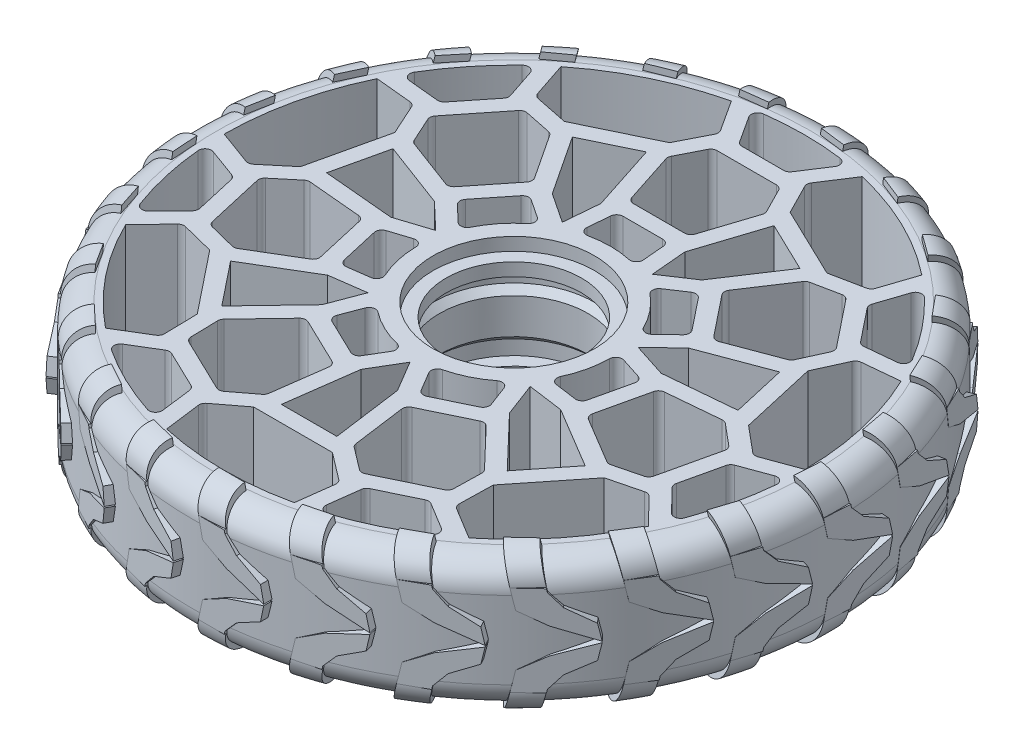
SolidWorks part; units mm, degrees
ref_plane "Front Plane" through (0, 0, 0) normal (0, 0, 1) x (1, 0, 0)
ref_plane "Top Plane" through (0, 0, 0) normal (0, 1, 0) x (1, 0, 0)
ref_plane "Right Plane" through (0, 0, 0) normal (1, 0, 0) x (0, 0, -1)
sketch "Sketch1" plane through (0, 0, 0) normal (0, 1, 0) x (1, 0, 0)
  circle A0 centre (0, 0) radius 19.05
  circle A1 centre (0, 0) radius 57.15
  circle A2 centre (0, 0) radius 63.5
  dimension "D1" = 127
  dimension "D2" = 114.3
  dimension "D3" = 38.1
extrude "Boss-Extrude1" add sketch "Sketch1" along normal blind 25.4 contours A2 A1 | A0
sketch "Sketch2" plane through (0, 25.4, 0) normal (0, 1, 0) x (1, 0, 0)
  line L1 (-5.0658, 25.4) -> (5.0658, 25.4)
  line L3 (-5.9462, 28.575) -> (5.9462, 28.575)
  line L4 (5.9462, 28.575) -> (9.6276, 39.9052)
  line L5 (9.6276, 39.9052) -> (6.6026, 45.8421)
  line L6 (6.6026, 45.8421) -> (-6.6026, 45.8421)
  line L7 (-6.6026, 45.8421) -> (-9.6276, 39.9052)
  line L8 (-9.6276, 39.9052) -> (-5.9462, 28.575)
  line L9 (-9.525, 56.3507) -> (-4.7625, 49.0171)
  line L10 (-4.7625, 49.0171) -> (4.7625, 49.0171)
  line L11 (4.7625, 49.0171) -> (9.525, 56.3507)
  line L12 (-8.253, 25.4) -> (-13.0536, 40.1748)
  line L13 (-13.0536, 40.1748) -> (-8.5483, 49.0171)
  line L14 (-8.5483, 49.0171) -> (-12.8757, 55.6807)
  line L15 (12.8757, 55.6807) -> (8.5483, 49.0171)
  line L16 (8.5483, 49.0171) -> (13.0536, 40.1748)
  line L17 (13.0536, 40.1748) -> (8.253, 25.4)
  line L18 (0, 0) -> (66.475, 0) construction
  line L19 (0, 0) -> (5.8868, 18.1176) construction
  line L20 (0, 0) -> (-5.8868, 18.1176) construction
  line L21 (0, 0) -> (-66.2004, 0) construction
  line L22 (-9.0065, 16.7864) -> (-8.253, 25.4)
  line L23 (-8.253, 25.4) -> (-20.404, 62.7971) construction
  line L24 (-5.0658, 25.4) -> (-5.6977, 18.178)
  line L25 (8.253, 25.4) -> (9.0065, 16.7864)
  line L26 (8.253, 25.4) -> (19.9506, 61.4016) construction
  line L27 (5.0658, 25.4) -> (5.6977, 18.178)
  circle A0 centre (0, 0) radius 19.05 construction
  circle A1 centre (0, 0) radius 57.15 construction
  arc A2 (-9.0065, 16.7864) -> (-5.6977, 18.178) centre (0, 0) cw
  arc A3 (5.6977, 18.178) -> (9.0065, 16.7864) centre (0, 0) cw
  arc A4 (-12.8757, 55.6807) -> (-9.525, 56.3507) centre (0, 0) cw
  arc A5 (9.525, 56.3507) -> (12.8757, 55.6807) centre (0, 0) cw
  point P35 (0, 49.0171)
  point P36 (0, 45.8421)
  point P42 (0, 28.575)
  dimension "D1" = 72
  dimension "D2" = 72
  dimension "D7" = 3.175
  dimension "D8" = 45
  dimension "D9" = 120
  dimension "D11" = 45
  dimension "D13" = 120
  dimension "D14" = 3.175
  dimension "D3" = 3.175
  dimension "D5" = 3.175
  dimension "D4" = 3.175
  dimension "D6" = 95
  dimension "D18" = 95
  dimension "D19" = 19.05
  dimension "D15" = 3.175
  dimension "D10" = 3.175
  dimension "D12" = 3.175
  dimension "D16" = 9.525
  dimension "D17" = 25.4
extrude "Boss-Extrude2" add sketch "Sketch2" against normal up to surface (25.4 mm away) up to face at (0, 0, 19.05)
fillet "Fillet1" radius 1.27 18 edges at (-8.5483, 12.7, -49.0171) (8.5483, 12.7, -49.0171) (-9.525, 12.7, -56.3507) (9.525, 12.7, -56.3507) (4.7625, 12.7, -49.0171) (-4.7625, 12.7, -49.0171) (-5.9462, 12.7, -28.575) (5.9462, 12.7, -28.575) (9.6276, 12.7, -39.9052) (6.6026, 12.7, -45.8421) (-6.6026, 12.7, -45.8421) (-9.6276, 12.7, -39.9052) (9.0065, 12.7, -16.7864) (-9.0065, 12.7, -16.7864) (5.6977, 12.7, -18.178) (5.0658, 12.7, -25.4) (-5.0658, 12.7, -25.4) (-5.6977, 12.7, -18.178)
pattern_circular "CirPattern1" count 7 over 360 about axis through (0, 0, 0) along (0, 1, 0) of "Boss-Extrude2", "Fillet1"
sketch "Sketch3" plane through (0, 25.4, 0) normal (0, 1, 0) x (1, 0, 0)
  line L0 (-36.2629, -21.6661) -> (-29.1921, -30.5325) construction
  line L2 (-45.1749, -19.4204) -> (-36.2629, -21.6661) construction
  line L3 (-38.804, -21.0257) -> (-29.1333, -33.1524)
  line L4 (-29.1921, -30.5325) -> (-28.9859, -39.7208) construction
  line L6 (-38.804, -21.0257) -> (-34.8876, -20.8444)
  line L7 (-36.2629, -21.6661) -> (-22.9267, -13.6981) construction
  line L8 (-34.8876, -20.8444) -> (-28.085, -29.3746)
  line L9 (-18.4563, -19.3038) -> (-29.1921, -30.5325) construction
  line L11 (-29.1333, -33.1524) -> (-28.085, -29.3746)
  dimension "D1" = 3.175
  dimension "D2" = 1.5875
extrude "Boss-Extrude3" add sketch "Sketch3" against normal up to surface (25.4 mm away) contours L11 L8 L6 L3 up to face at (-18.2195, 0, -37.8331)
pattern_circular "CirPattern2" count 7 over 360 about axis through (0, 0, 0) along (0, 1, 0) of "Boss-Extrude3"
sketch "Sketch4" plane through (0, 25.4, 0) normal (0, 1, 0) x (1, 0, 0)
  circle A0 centre (0, 0) radius 15.875
  dimension "D1" = 31.75
extrude "Cut-Extrude1" cut sketch "Sketch4" against normal up to surface (25.4 mm away) up to face at (-30.0096, 0, -6.8495)
ref_plane "Plane1" through (0, 0, 63.5) normal (0, 0, 1) x (1, 0, 0)
fillet "Fillet2" radius 5.08 2 edges at (0, 25.4, 63.5) (0, 0, 63.5)
sketch "Sketch5" plane through (0, 0, 63.5) normal (0, 0, 1) x (1, 0, 0)
  line L0 (0, 0) -> (0, 25.4) construction
  line L1 (38.0762, 12.7) -> (-38.0762, 12.7) construction
  line L2 (0, -3.175) -> (5.08, -3.175)
  line L3 (5.08, -3.175) -> (6.6661, 4.445)
  line L4 (0, -3.175) -> (2.247, 7.62)
  line L5 (6.6661, 4.445) -> (8.9338, 6.985)
  line L6 (8.9338, 6.985) -> (13.6627, 9.525)
  line L7 (13.6627, 9.525) -> (14.2971, 12.573)
  line L8 (14.2971, 12.573) -> (6.9759, 10.16)
  line L9 (2.247, 7.62) -> (6.9759, 10.16)
  line L10 (2.247, 17.78) -> (6.9759, 15.24)
  line L11 (14.2971, 12.827) -> (6.9759, 15.24)
  line L12 (13.6627, 15.875) -> (14.2971, 12.827)
  line L13 (8.9338, 18.415) -> (13.6627, 15.875)
  line L14 (6.6661, 20.955) -> (8.9338, 18.415)
  line L15 (0, 28.575) -> (2.247, 17.78)
  line L16 (5.08, 28.575) -> (6.6661, 20.955)
  line L17 (0, 28.575) -> (5.08, 28.575)
  point P7 (0, 12.7)
  dimension "D1" = 15.875
  dimension "D2" = 5.08
  dimension "D3" = 2.54
  dimension "D4" = 7.62
  dimension "D5" = 2.54
  dimension "D6" = 2.54
  dimension "D7" = 5.08
  dimension "D8" = 30
  dimension "D9" = 20
  dimension "D10" = 130
  dimension "D11" = 170
  dimension "D12" = 0.127
extrude "Boss-Extrude5" add sketch "Sketch5" against normal blind 5.08
pattern_circular "CirPattern3" count 25 over 360 about axis through (0, 0, 0) along (0, 1, 0) of "Boss-Extrude5"
ref_plane "Plane2" through (0, 0, 0) normal (1, 0, 0) x (0, 0, -1)
sketch "Sketch7" plane through (0, 0, 0) normal (1, 0, 0) x (0, 0, -1)
  line L6 (-63.5, 12.7) -> (-70.1627, 12.7) construction
  line L7 (-63.5, 20.32) -> (-63.5, 5.08) construction
  line L9 (-57.785, -1.2302) -> (-54.61, -1.2302)
  line L10 (-54.61, -1.2302) -> (-54.61, -3.81)
  line L11 (-54.61, -3.81) -> (-64.77, -3.81)
  line L12 (-58.42, 26.67) -> (-55.245, 26.67)
  line L22 (-63.5, 3.81) -> (-64.77, 3.81)
  line L23 (-64.77, 3.81) -> (-64.77, -3.81)
  line L26 (-63.5, 21.59) -> (-65.405, 21.59)
  line L27 (-65.405, 21.59) -> (-65.405, 29.21)
  line L30 (-55.245, 26.67) -> (-55.245, 29.21)
  line L31 (-55.245, 29.21) -> (-65.405, 29.21)
  line L32 (-63.5, 12.7) -> (63.5, 12.7) construction
  line L33 (63.5, 10.4839) -> (63.5, 14.9161) construction
  line L34 (0, 12.7) -> (0, 37.2998) construction
  arc A0 (-57.785, -1.2302) -> (-63.5, 3.81) centre (-58.42, 3.81) cw
  arc A1 (-58.42, 26.67) -> (-63.5, 21.59) centre (-58.42, 21.59) ccw
  point P10 (-63.5, -3.175)
  point P13 (-63.5, 28.575)
  dimension "D5" = 5.08
  dimension "D1" = 8.89
  dimension "D2" = 8.89
  dimension "D3" = 3.175
  dimension "D4" = 10.16
  dimension "D6" = 7.62
  dimension "D7" = 1.27
  dimension "D8" = 3.175
  dimension "D9" = 7.62
  dimension "D10" = 10.16
revolve "Cut-Revolve2" cut sketch "Sketch7" angle 360 about L34
sketch "Sketch10" plane through (0, 0, 0) normal (1, 0, 0) x (0, 0, -1)
  line L1 (-15.875, 22.86) -> (-13.335, 22.86)
  line L2 (-15.875, 22.86) -> (-15.875, 20.32)
  line L3 (-15.875, 20.32) -> (-13.335, 20.32)
  line L4 (-13.335, 22.86) -> (-13.335, 20.32)
  line L8 (-14.605, 16.1925) -> (-14.605, 9.2075)
  line L9 (-15.875, 5.08) -> (-13.335, 5.08)
  line L10 (-15.875, 5.08) -> (-15.875, 2.54)
  line L11 (-15.875, 2.54) -> (-13.335, 2.54)
  line L12 (-13.335, 5.08) -> (-13.335, 2.54)
  line L13 (-15.875, 25.4) -> (-15.875, -21.4861) construction
  line L14 (-15.875, 0) -> (15.875, 0) construction
  line L15 (-14.605, 16.1925) -> (-15.875, 17.4625)
  line L16 (-15.875, 17.4625) -> (-15.875, 7.9375)
  line L17 (-15.875, 7.9375) -> (-14.605, 9.2075)
  line L19 (0, 0) -> (0, 28.7302) construction
  point P4 (-15.875, 12.7)
  dimension "D1" = 2.54
  dimension "D2" = 2.54
  dimension "D3" = 2.54
  dimension "D4" = 2.54
  dimension "D5" = 1.27
  dimension "D6" = 1.27
  dimension "D7" = 1.27
  dimension "D8" = 9.525
  dimension "D9" = 12.7
revolve "Revolve1" add sketch "Sketch10" angle 360 about L19
equation "\"Wall\"=0.125"
equation "\"D7@Sketch2\"=\"Wall\""
equation "\"D14@Sketch2\"=\"Wall\""
equation "\"D3@Sketch2\"=\"Wall\""
equation "\"D5@Sketch2\"=\"Wall\""
equation "\"D4@Sketch2\"=\"Wall\""
equation "\"D15@Sketch2\"=\"Wall\""
equation "\"D10@Sketch2\"=\"Wall\""
equation "\"D12@Sketch2\"=\"Wall\""
equation "\"D1@Sketch3\"=\"Wall\""
equation "\"D2@Sketch3\"=\"Wall\"/2"
